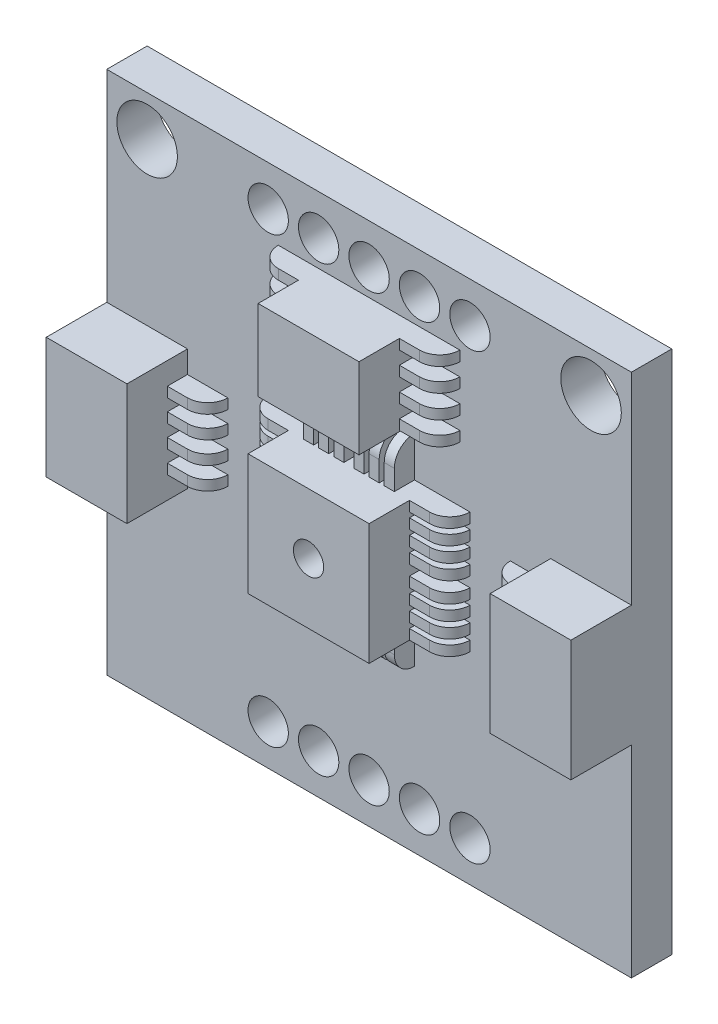
SolidWorks part; units mm, degrees
ref_plane "Front Plane" through (0, 0, 0) normal (0, 0, 1) x (1, 0, 0)
ref_plane "Top Plane" through (0, 0, 0) normal (0, 1, 0) x (1, 0, 0)
ref_plane "Right Plane" through (0, 0, 0) normal (1, 0, 0) x (0, 0, -1)
sketch "Sketch1" plane through (0, 0, 0) normal (0, 0, 1) x (1, 0, 0)
  line L1 (-13, 13) -> (13, 13)
  line L2 (-13, 13) -> (-13, -13)
  line L3 (-13, -13) -> (13, -13)
  line L4 (13, 13) -> (13, -13)
  line L5 (-13, 13) -> (13, -13) construction
  line L6 (-13, -13) -> (13, 13) construction
  point P0 (0, 0)
  dimension "D1" = 26
  dimension "D2" = 26
extrude "Boss-Extrude1" add sketch "Sketch1" along normal mid plane 2
sketch "Sketch2" plane through (0, 0, 1) normal (0, 0, 1) x (1, 0, 0)
  line L0 (0, -0.2408) -> (0, 13) construction
  line L1 (13, 13) -> (-13, 13) construction
  line L2 (-13, 0) -> (13, 0) construction
  line L3 (-13, 13) -> (-13, -13) construction
  line L4 (13, -13) -> (13, 13) construction
  line L6 (-3, 3) -> (3, 3)
  line L7 (-3, 3) -> (-3, -3)
  line L8 (-3, -3) -> (3, -3)
  line L9 (3, 3) -> (3, -3)
  line L10 (-3, 3) -> (3, -3) construction
  line L11 (-3, -3) -> (3, 3) construction
  circle A0 centre (0, 0) radius 2.2087 construction
  circle A1 centre (0, 0) radius 0.75
  dimension "D3" = 1.5
  dimension "D1" = 6
  dimension "D2" = 6
extrude "Boss-Extrude2" add sketch "Sketch2" along normal blind 3
sketch "Sketch4" plane through (0, 0, 1) normal (0, 0, 1) x (1, 0, 0)
  line L0 (0, 3) -> (0, -3) construction
  line L1 (3, 3) -> (-3, 3) construction
  line L2 (-3, -3) -> (3, -3) construction
  line L3 (-3, 0) -> (3, 0) construction
  line L4 (-3, 3) -> (-5, 3)
  line L5 (-3, 3) -> (-3, 2.5)
  line L6 (-3, 2.5) -> (-5, 2.5)
  line L7 (-5, 3) -> (-5, 2.5)
  line L8 (-3, 3) -> (-3, -3) construction
  line L9 (3, -3) -> (3, 3) construction
  line L10 (-3, 2.25) -> (-5, 2.25)
  line L11 (-3, 2.25) -> (-3, 1.75)
  line L12 (-3, 1.75) -> (-5, 1.75)
  line L13 (-5, 2.25) -> (-5, 1.75)
  line L14 (-3, 1.5) -> (-5, 1.5)
  line L15 (-3, 1.5) -> (-3, 1)
  line L16 (-3, 1) -> (-5, 1)
  line L17 (-5, 1.5) -> (-5, 1)
  line L18 (-3, 0.75) -> (-5, 0.75)
  line L19 (-3, 0.75) -> (-3, 0.25)
  line L20 (-3, 0.25) -> (-5, 0.25)
  line L21 (-5, 0.75) -> (-5, 0.25)
  line L22 (-3, -0.25) -> (-5, -0.25)
  line L23 (-5, -0.75) -> (-5, -0.25)
  line L24 (-3, -0.75) -> (-3, -0.25)
  line L25 (-3, -0.75) -> (-5, -0.75)
  line L26 (-5, -1.5) -> (-5, -1)
  line L27 (-3, -1) -> (-5, -1)
  line L28 (-3, -1.5) -> (-3, -1)
  line L29 (-3, -1.5) -> (-5, -1.5)
  line L30 (-5, -2.25) -> (-5, -1.75)
  line L31 (-3, -1.75) -> (-5, -1.75)
  line L32 (-3, -2.25) -> (-3, -1.75)
  line L33 (-3, -2.25) -> (-5, -2.25)
  line L34 (-5, -3) -> (-5, -2.5)
  line L35 (-3, -2.5) -> (-5, -2.5)
  line L36 (-3, -3) -> (-3, -2.5)
  line L37 (-3, -3) -> (-5, -3)
  line L38 (3, 3) -> (5, 3)
  line L39 (3, -3) -> (5, -3)
  line L40 (3, -3) -> (3, -2.5)
  line L41 (3, -2.5) -> (5, -2.5)
  line L42 (5, -3) -> (5, -2.5)
  line L43 (3, -2.25) -> (5, -2.25)
  line L44 (3, -2.25) -> (3, -1.75)
  line L45 (3, -1.75) -> (5, -1.75)
  line L46 (5, -2.25) -> (5, -1.75)
  line L47 (3, -1.5) -> (5, -1.5)
  line L48 (3, -1.5) -> (3, -1)
  line L49 (3, -1) -> (5, -1)
  line L50 (5, -1.5) -> (5, -1)
  line L51 (3, -0.75) -> (5, -0.75)
  line L52 (3, -0.75) -> (3, -0.25)
  line L53 (5, -0.75) -> (5, -0.25)
  line L54 (3, -0.25) -> (5, -0.25)
  line L55 (5, 0.75) -> (5, 0.25)
  line L56 (3, 0.25) -> (5, 0.25)
  line L57 (3, 0.75) -> (3, 0.25)
  line L58 (3, 0.75) -> (5, 0.75)
  line L59 (5, 1.5) -> (5, 1)
  line L60 (3, 1) -> (5, 1)
  line L61 (3, 1.5) -> (3, 1)
  line L62 (3, 1.5) -> (5, 1.5)
  line L63 (5, 2.25) -> (5, 1.75)
  line L64 (3, 1.75) -> (5, 1.75)
  line L65 (3, 2.25) -> (3, 1.75)
  line L66 (3, 2.25) -> (5, 2.25)
  line L67 (5, 3) -> (5, 2.5)
  line L68 (3, 2.5) -> (5, 2.5)
  line L69 (3, 3) -> (3, 2.5)
  line L70 (-1.75, -3) -> (-1.75, -5)
  line L75 (-2.25, -3) -> (-1.75, -3)
  line L76 (-2.25, -3) -> (-2.25, -5)
  line L77 (-2.25, -5) -> (-1.75, -5)
  line L78 (-1, -3) -> (-1, -5)
  line L79 (-1.5, -3) -> (-1, -3)
  line L80 (-1.5, -3) -> (-1.5, -5)
  line L81 (-1.5, -5) -> (-1, -5)
  line L82 (-0.25, -3) -> (-0.25, -5)
  line L83 (-0.75, -3) -> (-0.25, -3)
  line L84 (-0.75, -3) -> (-0.75, -5)
  line L85 (-0.75, -5) -> (-0.25, -5)
  line L86 (0.75, -5) -> (0.25, -5)
  line L87 (0.75, -3) -> (0.75, -5)
  line L88 (0.75, -3) -> (0.25, -3)
  line L89 (0.25, -3) -> (0.25, -5)
  line L90 (1.5, -5) -> (1, -5)
  line L91 (1.5, -3) -> (1.5, -5)
  line L92 (1.5, -3) -> (1, -3)
  line L93 (1, -3) -> (1, -5)
  line L94 (2.25, -5) -> (1.75, -5)
  line L95 (2.25, -3) -> (2.25, -5)
  line L96 (2.25, -3) -> (1.75, -3)
  line L101 (1.75, -3) -> (1.75, -5)
  line L104 (1.75, 3) -> (1.75, 5)
  line L109 (2.25, 3) -> (1.75, 3)
  line L110 (2.25, 3) -> (2.25, 5)
  line L111 (2.25, 5) -> (1.75, 5)
  line L112 (1, 3) -> (1, 5)
  line L113 (1.5, 3) -> (1, 3)
  line L114 (1.5, 3) -> (1.5, 5)
  line L115 (1.5, 5) -> (1, 5)
  line L116 (0.25, 3) -> (0.25, 5)
  line L117 (0.75, 3) -> (0.25, 3)
  line L118 (0.75, 3) -> (0.75, 5)
  line L119 (0.75, 5) -> (0.25, 5)
  line L120 (-0.75, 5) -> (-0.25, 5)
  line L121 (-0.75, 3) -> (-0.75, 5)
  line L122 (-0.75, 3) -> (-0.25, 3)
  line L123 (-0.25, 3) -> (-0.25, 5)
  line L124 (-1.5, 5) -> (-1, 5)
  line L125 (-1.5, 3) -> (-1.5, 5)
  line L126 (-1.5, 3) -> (-1, 3)
  line L127 (-1, 3) -> (-1, 5)
  line L128 (-2.25, 5) -> (-1.75, 5)
  line L129 (-2.25, 3) -> (-2.25, 5)
  line L130 (-2.25, 3) -> (-1.75, 3)
  line L135 (-1.75, 3) -> (-1.75, 5)
  point P137 (0, 0)
  dimension "D2" = 0.5
  dimension "D3" = 4
extrude "Boss-Extrude3" add sketch "Sketch4" along normal blind 1
fillet "Fillet1" radius 1 28 edges at (2, 5, 2) (1.25, 5, 2) (0.5, 5, 2) (-0.5, 5, 2) (-1.25, 5, 2) (-2, 5, 2) (-5, 0.5, 2) (-5, 1.25, 2) (-5, 2, 2) (-5, 2.75, 2) (-5, -0.5, 2) (-5, -1.25, 2) (-5, -2, 2) (-5, -2.75, 2) (-2, -5, 2) (-1.25, -5, 2) (-0.5, -5, 2) (0.5, -5, 2) (1.25, -5, 2) (2, -5, 2) (5, 2.75, 2) (5, 2, 2) (5, 1.25, 2) (5, 0.5, 2) (5, -0.5, 2) (5, -1.25, 2) (5, -2, 2) (5, -2.75, 2)
sketch "Sketch5" plane through (0, 0, 1) normal (0, 0, 1) x (1, 0, 0)
  line L0 (0, 13) -> (0, -13) construction
  line L1 (13, 13) -> (-13, 13) construction
  line L2 (-13, -13) -> (13, -13) construction
  line L3 (-13, 0) -> (13, 0) construction
  line L4 (-13, 13) -> (-13, -13) construction
  line L5 (13, -13) -> (13, 13) construction
  line L7 (-2.5, 9.7) -> (2.5, 9.7)
  line L8 (-2.5, 9.7) -> (-2.5, 5.7)
  line L9 (-2.5, 5.7) -> (2.5, 5.7)
  line L10 (2.5, 9.7) -> (2.5, 5.7)
  line L11 (-13, 3) -> (-9, 3)
  line L12 (-13, 3) -> (-13, -3)
  line L13 (-13, -3) -> (-9, -3)
  line L14 (-9, 3) -> (-9, -3)
  line L15 (13, 3) -> (9, 3)
  line L16 (13, 3) -> (13, -3)
  line L17 (13, -3) -> (9, -3)
  line L18 (9, 3) -> (9, -3)
  point P16 (0, 5.7)
  point P25 (-9, 0)
  point P26 (9, 0)
  dimension "D1" = 4
  dimension "D2" = 3.3
  dimension "D3" = 5
  dimension "D4" = 4
  dimension "D5" = 6
  dimension "D6" = 6
  dimension "D7" = 4
extrude "Boss-Extrude4" add sketch "Sketch5" along normal blind 3
sketch "Sketch6" plane through (0, 0, 1) normal (0, 0, 1) x (1, 0, 0)
  line L0 (0, 9.7) -> (0, 5.7) construction
  line L1 (-2.5, 9.7) -> (-4.5, 9.7)
  line L2 (-2.5, 9.7) -> (-2.5, 9.2)
  line L3 (-2.5, 9.2) -> (-4.5, 9.2)
  line L4 (-4.5, 9.7) -> (-4.5, 9.2)
  line L5 (2.5, 9.7) -> (-2.5, 9.7) construction
  line L6 (-2.5, 5.7) -> (2.5, 5.7) construction
  line L7 (-2.5, 8.55) -> (-4.5, 8.55)
  line L8 (-2.5, 8.55) -> (-2.5, 8.05)
  line L9 (-9, 3) -> (-13, 3) construction
  line L10 (-13, -3) -> (-9, -3) construction
  line L11 (-13, -3) -> (-9, -3) construction
  line L13 (-2.5, 8.05) -> (-4.5, 8.05)
  line L14 (-4.5, 8.55) -> (-4.5, 8.05)
  line L15 (-2.5, 7.4) -> (-4.5, 7.4)
  line L16 (-2.5, 7.4) -> (-2.5, 6.9)
  line L17 (-2.5, 6.9) -> (-4.5, 6.9)
  line L18 (-4.5, 7.4) -> (-4.5, 6.9)
  line L19 (-2.5, 6.25) -> (-4.5, 6.25)
  line L20 (-2.5, 6.25) -> (-2.5, 5.75)
  line L21 (-2.5, 5.75) -> (-4.5, 5.75)
  line L22 (-4.5, 6.25) -> (-4.5, 5.75)
  line L23 (-9, 1.9) -> (-7, 1.9)
  line L24 (-9, 1.9) -> (-9, 1.4)
  line L25 (-9, 1.4) -> (-7, 1.4)
  line L26 (-7, 1.9) -> (-7, 1.4)
  line L27 (-9, 0.8) -> (-7, 0.8)
  line L28 (-9, 0.8) -> (-9, 0.3)
  line L29 (-9, 0.3) -> (-7, 0.3)
  line L30 (-7, 0.8) -> (-7, 0.3)
  line L31 (-9, -0.3) -> (-7, -0.3)
  line L32 (-9, -0.3) -> (-9, -0.8)
  line L33 (-9, -0.8) -> (-7, -0.8)
  line L34 (-7, -0.3) -> (-7, -0.8)
  line L35 (-9, -1.4) -> (-7, -1.4)
  line L36 (-9, -1.4) -> (-9, -1.9)
  line L37 (-9, -1.9) -> (-7, -1.9)
  line L38 (-7, -1.4) -> (-7, -1.9)
  line L39 (4.5, 6.25) -> (4.5, 5.75)
  line L40 (2.5, 5.75) -> (4.5, 5.75)
  line L41 (2.5, 6.25) -> (2.5, 5.75)
  line L42 (2.5, 6.25) -> (4.5, 6.25)
  line L43 (4.5, 7.4) -> (4.5, 6.9)
  line L44 (2.5, 6.9) -> (4.5, 6.9)
  line L45 (2.5, 7.4) -> (2.5, 6.9)
  line L46 (2.5, 7.4) -> (4.5, 7.4)
  line L47 (4.5, 8.55) -> (4.5, 8.05)
  line L48 (2.5, 8.05) -> (4.5, 8.05)
  line L49 (2.5, 8.55) -> (2.5, 8.05)
  line L50 (2.5, 8.55) -> (4.5, 8.55)
  line L51 (4.5, 9.7) -> (4.5, 9.2)
  line L52 (2.5, 9.2) -> (4.5, 9.2)
  line L53 (2.5, 9.7) -> (2.5, 9.2)
  line L54 (2.5, 9.7) -> (4.5, 9.7)
  line L55 (7, -1.4) -> (7, -1.9)
  line L56 (9, -1.9) -> (7, -1.9)
  line L57 (9, -1.4) -> (9, -1.9)
  line L58 (9, -1.4) -> (7, -1.4)
  line L59 (7, -0.3) -> (7, -0.8)
  line L60 (9, -0.8) -> (7, -0.8)
  line L61 (9, -0.3) -> (9, -0.8)
  line L62 (9, -0.3) -> (7, -0.3)
  line L63 (7, 0.8) -> (7, 0.3)
  line L64 (9, 0.3) -> (7, 0.3)
  line L65 (9, 0.8) -> (9, 0.3)
  line L66 (9, 0.8) -> (7, 0.8)
  line L67 (7, 1.9) -> (7, 1.4)
  line L68 (9, 1.4) -> (7, 1.4)
  line L69 (9, 1.9) -> (9, 1.4)
  line L70 (9, 1.9) -> (7, 1.9)
  dimension "D1" = 2
  dimension "D2" = 0.5
  dimension "D3" = 1.1
  dimension "D4" = 0.5
  dimension "D5" = 2
  dimension "D6" = 0.6
  dimension "D7" = 0.6
  dimension "D8" = 0.6
  dimension "D9" = 1.1
  dimension "D10" = 2.2
extrude "Boss-Extrude5" add sketch "Sketch6" along normal blind 1
fillet "Fillet2" radius 1 16 edges at (-4.5, 6, 2) (-4.5, 7.15, 2) (-4.5, 8.3, 2) (-4.5, 9.45, 2) (-7, -1.65, 2) (-7, -0.55, 2) (-7, 0.55, 2) (-7, 1.65, 2) (7, -1.65, 2) (7, 0.55, 2) (7, -0.55, 2) (7, 1.65, 2) (4.5, 6, 2) (4.5, 7.15, 2) (4.5, 8.3, 2) (4.5, 9.45, 2)
sketch "Sketch7" plane through (0, 0, 1) normal (0, 0, 1) x (1, 0, 0)
  line L0 (-13, 11) -> (13, 11) construction
  line L1 (-13, 13) -> (-13, 3) construction
  line L2 (13, 3) -> (13, 13) construction
  line L3 (13, 13) -> (-13, 13) construction
  line L4 (-13, 0) -> (13, 0) construction
  line L5 (-13, 3) -> (-13, -3) construction
  line L6 (13, -3) -> (13, 3) construction
  circle A0 centre (-11, 11) radius 1.5
  circle A1 centre (11, 11) radius 1.5
  circle A2 centre (-5, 11) radius 1
  circle A3 centre (-2.5, 11) radius 1
  circle A4 centre (0, 11) radius 1
  circle A5 centre (2.5, 11) radius 1
  circle A6 centre (5, 11) radius 1
  circle A7 centre (5, -11) radius 1
  circle A8 centre (2.5, -11) radius 1
  circle A9 centre (0, -11) radius 1
  circle A10 centre (-2.5, -11) radius 1
  circle A11 centre (-5, -11) radius 1
  dimension "D2" = 3
  dimension "D3" = 2
  dimension "D4" = 2
  dimension "D5" = 3
  dimension "D6" = 2
  dimension "D7" = 8
  dimension "D1" = 2
  dimension "D8" = 5
extrude "Cut-Extrude1" cut sketch "Sketch7" against normal blind 21
